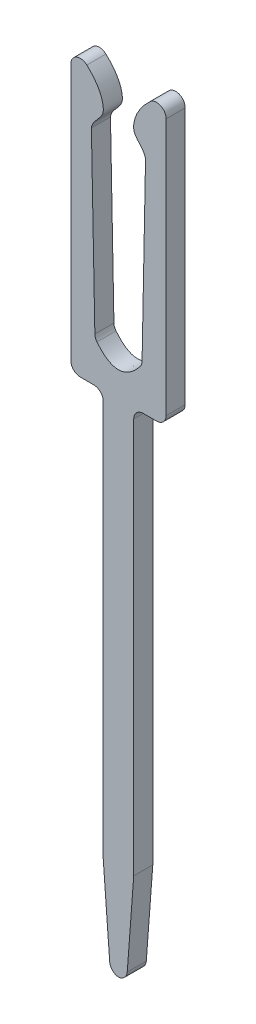
SolidWorks part; units mm, degrees
material "1060 Alloy"
ref_plane "Front Plane" through (0, 0, 0) normal (0, 0, 1) x (1, 0, 0)
ref_plane "Top Plane" through (0, 0, 0) normal (0, 1, 0) x (1, 0, 0)
ref_plane "Right Plane" through (0, 0, 0) normal (1, 0, 0) x (0, 0, -1)
sketch "Sketch1" plane through (0, 0, 0) normal (0, 0, 1) x (1, 0, 0)
  line L0 (-0.32, 1.9994) -> (-0.32, 10.2994)
  line L1 (-0.1839, 0.1844) -> (-0.32, 1.9994)
  line L2 (-0.5677, 15.141) -> (-0.4952, 11.4343)
  line L3 (-1, 10.6994) -> (-1, 16.0898)
  line L4 (0.1839, 0.1844) -> (0.32, 1.9994)
  line L5 (0.32, 1.9994) -> (0.32, 10.2994)
  line L6 (0.52, 10.4994) -> (0.8, 10.4994)
  line L7 (1, 10.6994) -> (1, 16.0898)
  line L8 (0.5677, 15.141) -> (0.4952, 11.4343)
  line L9 (-0.52, 10.4994) -> (-0.8, 10.4994)
  line L10 (0, 11.0326) -> (0, 0) construction
  arc A0 (0, 0) -> (-0.1839, 0.1844) centre (0.0156, 0.1994) cw
  arc A1 (-0.4952, 11.4343) -> (-0.4511, 11.3128) centre (-0.2953, 11.4382) ccw
  arc A2 (-1, 16.0898) -> (-0.663, 16.2356) centre (-0.8, 16.0898) cw
  arc A3 (-0.8, 10.4994) -> (-1, 10.6994) centre (-0.8, 10.6994) cw
  arc A4 (0, 0) -> (0.1839, 0.1844) centre (-0.0156, 0.1994) ccw
  arc A5 (0.32, 10.2994) -> (0.52, 10.4994) centre (0.52, 10.2994) cw
  arc A6 (0.8, 10.4994) -> (1, 10.6994) centre (0.8, 10.6994) ccw
  arc A7 (1, 16.0898) -> (0.663, 16.2356) centre (0.8, 16.0898) ccw
  arc A8 (0.4952, 11.4343) -> (0.4511, 11.3128) centre (0.2953, 11.4382) cw
  arc A9 (-0.32, 10.2994) -> (-0.52, 10.4994) centre (-0.52, 10.2994) ccw
  spline S0 degree 3 poles (0.663, 16.2356) (0.4876, 16.0707) (0.3262, 15.8488) (0.3107, 15.4209) (0.5485, 15.3086) (0.5677, 15.141) knots 0.253308 0.253308 0.253308 0.253308 0.663172 0.707067 1 1 1 1
  spline S1 degree 2 poles (-0.4511, 11.3128) (0, 10.7524) (0.4511, 11.3128) knots 0.043405 0.043405 0.043405 0.956595 0.956595 0.956595
  spline S2 degree 3 poles (-0.663, 16.2356) (-0.4876, 16.0707) (-0.3262, 15.8488) (-0.3107, 15.4209) (-0.5485, 15.3086) (-0.5677, 15.141) knots 0.253308 0.253308 0.253308 0.253308 0.663172 0.707067 1 1 1 1
  dimension "D2" = 0.2
  dimension "D7" = 0.2
  dimension "D8" = 0.68
  dimension "D10" = 0.2
  dimension "D13" = 0.2
  dimension "D1" = 11.0326
  dimension "D3" = 0.1839
  dimension "D4" = 1.815
  dimension "D6" = 8.3
  dimension "D9" = 5.3904
  dimension "D11" = 0.8134
  dimension "D12" = 0.1215
  dimension "D14" = 0.4323
  dimension "D15" = 0.337
  dimension "D16" = 0.9489
  dimension "D17" = 0.5048
extrude "Boss-Extrude1" add sketch "Sketch1" against normal mid plane 0.4
ref_axis "Axis1" through (0, 11.0326, 0) along (0, -1, 0)
sketch "Sketch2" plane through (0, 0, 0) normal (1, 0, 0) x (0, 0, -1)
  line L0 (0, 19.6692) -> (0, -4.3261) construction
